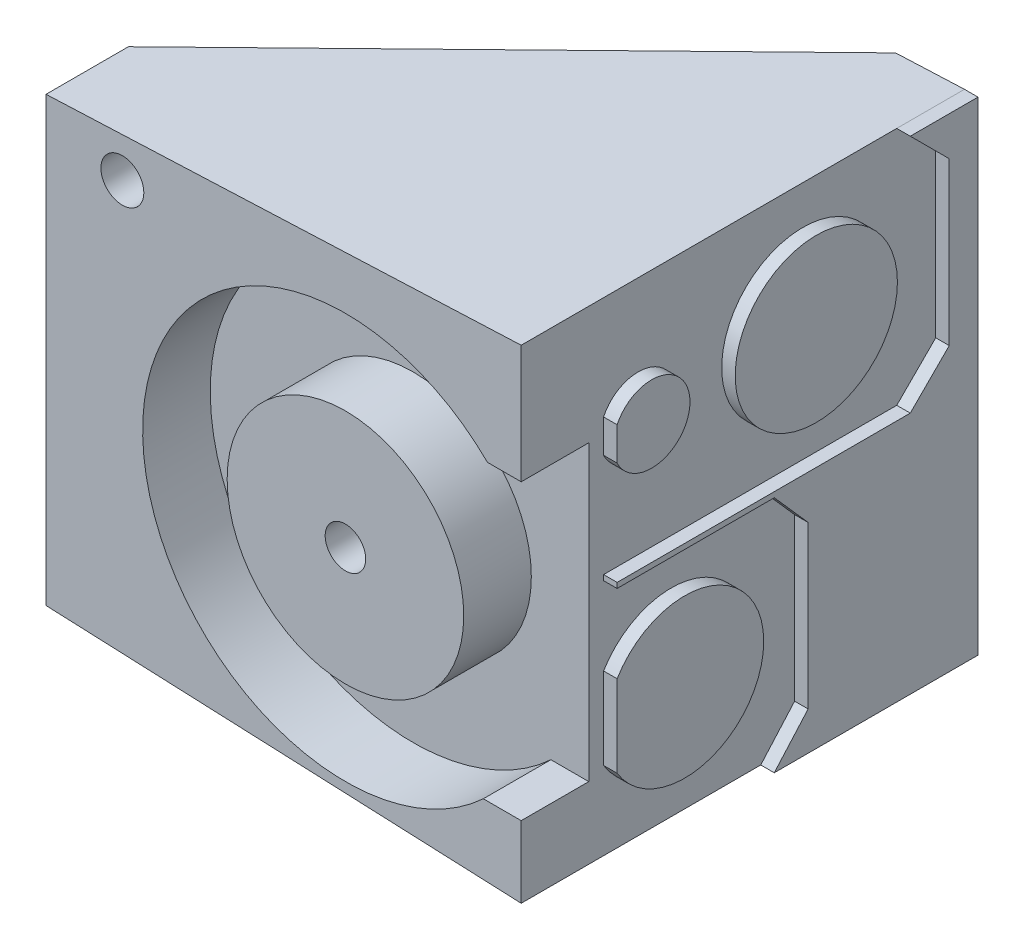
SolidWorks part; units mm, degrees
material "Aleación 1060"
ref_plane "Alzado" through (0, 0, 0) normal (0, 0, 1) x (1, 0, 0)
ref_plane "Planta" through (0, 0, 0) normal (0, 1, 0) x (1, 0, 0)
ref_plane "Vista lateral" through (0, 0, 0) normal (1, 0, 0) x (0, 0, -1)
sketch "Croquis1" plane through (0, 0, 0) normal (0, 1, 0) x (1, 0, 0)
  line L1 (-36.15, -32.79) -> (36.15, -32.79)
  line L2 (-36.15, -32.79) -> (-36.15, 32.79)
  line L3 (-36.15, 32.79) -> (36.15, 32.79)
  line L4 (36.15, -32.79) -> (36.15, 32.79)
  line L5 (-36.15, -32.79) -> (36.15, 32.79) construction
  line L6 (-36.15, 32.79) -> (36.15, -32.79) construction
  point P0 (0, 0)
  dimension "D1" = 72.3
  dimension "D2" = 65.58
extrude "Saliente-Extruir1" add sketch "Croquis1" along normal mid plane 71.5
sketch "Croquis2" plane through (36.15, 0, 0) normal (1, 0, 0) x (0, 0, -1)
  line L4 (-20.6, 35.75) -> (-32.79, 35.75)
  line L5 (-32.79, 35.75) -> (-32.79, -35.75)
  line L6 (-32.79, -35.75) -> (-20.6, -35.75)
  line L14 (-20.6, 35.75) -> (-20.6, -35.75)
  line L15 (-32.79, 35.75) -> (32.79, 35.75) construction
  line L16 (-32.79, -35.75) -> (32.79, -35.75) construction
  line L17 (-20.6, 35.75) -> (22.77, 35.75)
  line L18 (22.77, 35.75) -> (28.535, 29.985)
  line L19 (28.535, 29.985) -> (28.535, 6.035)
  line L20 (28.535, 6.035) -> (22.77, 0.27)
  line L21 (22.77, 0.27) -> (-20.6, 0.27)
  line L22 (-20.6, -0.51) -> (2.65, -0.51)
  line L23 (2.65, -0.51) -> (7.66, -6.18)
  line L24 (7.66, -6.18) -> (7.66, -30.08)
  line L25 (7.66, -30.08) -> (2.65, -35.75)
  line L26 (2.65, -35.75) -> (-20.6, -35.75)
  line L27 (32.79, 35.75) -> (32.79, -35.75) construction
  circle A3 centre (8.87, 18.01) radius 12
  arc A4 (-20.6, 15.553) -> (-20.6, 20.467) centre (-15.49, 18.01) ccw
  arc A5 (-20.6, -24.1844) -> (-20.6, -12.0756) centre (-10.6, -18.13) ccw
  line M19 (-32.79, -35.75) -> (32.79, -35.75)
  line M21 (32.79, 35.75) -> (-32.79, 35.75)
  line M22 (-32.79, 35.75) -> (-32.79, -35.75)
  dimension "D28" = 23.38
  dimension "D32" = 24
  dimension "D33" = 11.34
  dimension "D19" = 35.48
  dimension "D20" = 53.39
  dimension "D21" = 35.24
  dimension "D22" = 23.95
  dimension "D23" = 43.37
  dimension "D24" = 28.26
  dimension "D25" = 23.9
  dimension "D26" = 23.25
  dimension "D27" = 17.62
  dimension "D29" = 17.74
  dimension "D30" = 5.11
  dimension "D31" = 24.36
  dimension "D34" = 10
extrude "Cortar-Extruir1" cut sketch "Croquis2" against normal blind 2 contours L14 M21 M22 M19 | A4 L14 L21 L20 L19 L18 A3 M21 | A5 L14 L25 L24 L23 L22 M19 region at (36.15, 0, 26.695) region at (36.15, 35.1439, -1.085) region at (36.15, -29.9672, 20.1483)
sketch "Croquis3" plane through (0, 0, 32.79) normal (0, 0, 1) x (1, 0, 0)
  line L0 (34.15, 35.75) -> (-36.15, 32.3656)
  line L1 (-36.15, 32.3656) -> (-36.15, -32.7756)
  line L2 (-36.15, -32.7756) -> (34.15, -36.16)
  line L3 (34.15, -36.16) -> (34.15, 35.75)
  line L4 (34.15, -25.16) -> (28.5461, -25.16)
  line L5 (34.15, 18.25) -> (29.1646, 18.25)
  line L6 (34.15, -25.16) -> (34.15, 18.25)
  circle A0 centre (28.9, 30.2412) radius 3.5
  circle A1 centre (28.9, -30.6512) radius 3.5
  arc A2 (29.1646, 18.25) -> (28.5461, -25.16) centre (8.15, -3.16) ccw
  circle A3 centre (8.15, -3.16) radius 17.5
  circle A4 centre (8.15, -3.16) radius 3
  circle A5 centre (-24.8529, 27.3656) radius 3.175
  dimension "D4" = 7
  dimension "D9" = 6.35
  dimension "D10" = 6
  dimension "D11" = 35
  dimension "D12" = 60
  dimension "D1" = 70.3
  dimension "D2" = 71.91
  dimension "D3" = 65.1413
  dimension "D5" = 5.25
  dimension "D6" = 5.25
  dimension "D7" = 5.25
  dimension "D8" = 5.25
  dimension "D13" = 26
  dimension "D14" = 33
  dimension "D15" = 5
  dimension "D16" = 11.2971
  dimension "D17" = 11
  dimension "D18" = 17.5
extrude "Cortar-Extruir2" cut sketch "Croquis3" against normal blind 10 contours L5 A2 L4 L3 A3 | A4 region at (33.3293, -3.455, 32.79) region at (8.15, -3.16, 32.79)
sketch "Croquis4" plane through (0, 0, 0) normal (0, 1, 0) x (1, 0, 0)
  line L0 (-36.15, 32.79) -> (23.958, 32.79)
  line L1 (36.15, 32.79) -> (-36.15, 32.79) construction
  line L2 (23.958, 32.79) -> (-36.15, -20.6)
  line L3 (-36.15, 32.79) -> (-36.15, -32.79) construction
  line L4 (-36.15, -20.6) -> (-36.15, 32.79)
  dimension "D1" = 12.192
  dimension "D2" = 12.19
extrude "Cortar-Extruir3" cut sketch "Croquis4" against normal through all both and the other way through all
sketch "Croquis5" plane through (0, 0, 0) normal (0, 1, 0) x (1, 0, 0)
  line L0 (23.958, 32.79) -> (23.958, -20.6)
  line L1 (23.958, -20.6) -> (-36.15, -20.6)
  line L2 (-36.15, -20.6) -> (23.958, 32.79)
extrude "Cortar-Extruir4" cut sketch "Croquis5" against normal mid plane 62
extrude "Cortar-Extruir5" cut sketch "Croquis3<3>" against normal through all contours A5 region at (-24.8529, 27.3656, 32.79)
sketch "Croquis3<3>" plane through (0, 0, 32.79) normal (0, 0, 1) x (1, 0, 0) same geometry as "Croquis3"
sketch "Croquis6" plane through (0, 0, 32.79) normal (0, 0, 1) x (1, 0, 0)
  line L6 (-36.15, 32.75) -> (-36.15, 35.75)
  line L7 (-36.15, 35.75) -> (-36.15, -35.75) construction
  line L8 (-36.15, 35.75) -> (34.15, 35.75)
  line L9 (34.15, 35.75) -> (-36.15, 32.75)
  line L10 (-36.15, -32.75) -> (-36.15, -35.75)
  line L11 (-36.15, -35.75) -> (34.15, -35.75)
  line L12 (34.15, -35.75) -> (-36.15, -32.75)
  dimension "D1" = 3
  dimension "D2" = 3
extrude "Cortar-Extruir6" cut sketch "Croquis6" against normal through all
